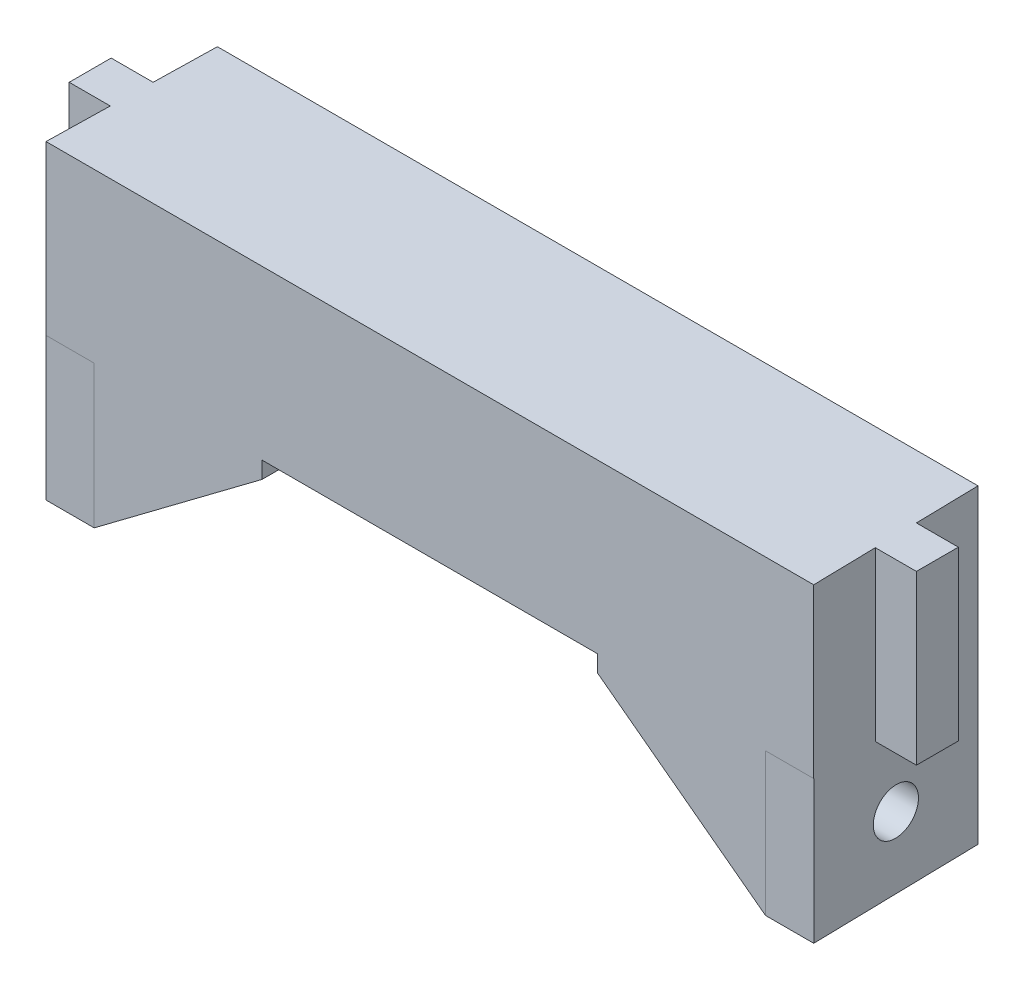
SolidWorks part; units mm, degrees
ref_plane "Front Plane" through (0, 0, 0) normal (0, 0, 1) x (1, 0, 0)
ref_plane "Top Plane" through (0, 0, 0) normal (0, 1, 0) x (1, 0, 0)
ref_plane "Right Plane" through (0, 0, 0) normal (1, 0, 0) x (0, 0, -1)
sketch "Sketch1" plane through (0, 0, 0) normal (0, 1, 0) x (1, 0, 0)
  line L0 (-45.74, 0) -> (-45.3158, 20)
  line L1 (-45.3158, 20) -> (45.3158, 20)
  line L2 (45.3158, 20) -> (45.74, 0)
  line L3 (45.74, 0) -> (-45.74, 0)
  point P4 (0, 0)
  point P7 (0, 20)
  dimension "D1" = 20
  dimension "D2" = 91.48
  dimension "D3" = 2.43
extrude "Boss-Extrude1" add sketch "Sketch1" along normal blind 20
sketch "Sketch2" plane through (0, 20, 0) normal (0, 1, 0) x (1, 0, 0)
  line L0 (45.74, 0) -> (45.3158, 20) construction
  line L1 (45.4749, 12.5) -> (50.4749, 12.5)
  line L2 (45.4749, 12.5) -> (45.4749, 7.5)
  line L3 (45.4749, 7.5) -> (50.4749, 7.5)
  line L4 (50.4749, 12.5) -> (50.4749, 7.5)
  line L5 (40.3158, 20) -> (40.3158, 0) construction
  line L6 (45.3158, 20) -> (-45.3158, 20) construction
  line L7 (-45.74, 0) -> (45.74, 0) construction
  line L8 (40.3158, 10) -> (45.5279, 10) construction
  line L9 (0, 0) -> (0, 20) construction
  line L10 (-45.4749, 7.5) -> (-50.4749, 7.5)
  line L11 (-50.4749, 12.5) -> (-50.4749, 7.5)
  line L12 (-45.4749, 12.5) -> (-50.4749, 12.5)
  line L13 (-45.4749, 12.5) -> (-45.4749, 7.5)
  point P14 (45.4749, 10)
  dimension "D1" = 5
  dimension "D2" = 5
  dimension "D3" = 5
extrude "Boss-Extrude2" add sketch "Sketch2" against normal up to surface (20 mm away) up to face at (0, 0, -10)
sketch "Sketch3" plane through (-45.7194, 0, -0.9697) normal (-0.9998, 0, -0.0212) x (-0.0212, 0, 0.9998)
  line L0 (0.9649, 0) -> (0.9649, -27.94) construction
  line L1 (-19.0346, 0) -> (0.9649, 0)
  line L2 (-19.0346, 0) -> (-19.0346, -17)
  line L3 (-19.0346, -17) -> (0.9649, -17)
  line L4 (0.9649, 0) -> (0.9649, -17)
  circle A0 centre (-9.0348, -8.5) radius 2.75 construction
  circle A1 centre (-9.0348, -8.5) radius 6.5 construction
  point P10 (-19.0346, -8.5)
  point P11 (-9.0348, 0)
  dimension "D2" = 5.5
  dimension "D3" = 13
  dimension "D1" = 17
ref_plane "Plane1" through (-40, 0, 0) normal (1, 0, 0) x (0, 0, -1)
sketch "Sketch4" plane through (-40, 0, 0) normal (1, 0, 0) x (0, 0, -1)
  line L4 (20, 0) -> (20, -17)
  line L5 (20, -17) -> (0, -17)
  line L6 (0, -17) -> (0, 0)
  line L7 (0, 0) -> (20, 0)
  line L11 (20, -17) -> (0.0049, -17) construction
  point P0 (0, 0)
loft "Loft1" add section "Sketch4" section "Sketch3" start constraint default connector at (-40, 0, -20) connector at (-45.3158, 0, -20)
ref_plane "Plane2" through (-20, 0, 0) normal (1, 0, 0) x (0, 0, -1)
sketch "Sketch5" plane through (-20, 0, 0) normal (1, 0, 0) x (0, 0, -1)
  line L1 (20, 0) -> (0, 0)
  line L2 (20, 0) -> (20, -2)
  line L3 (20, -2) -> (0, -2)
  line L4 (0, 0) -> (0, -2)
  point P5 (0, 0)
  dimension "D1" = 2
sketch "Sketch6" plane through (-40, 0, 0) normal (1, 0, 0) x (0, 0, -1)
  line L4 (20, 0) -> (0, 0)
  line L5 (0, 0) -> (0, -17)
  line L6 (0, -17) -> (20, -17)
  line L7 (20, -17) -> (20, 0)
  line L8 (20, 0) -> (0, 0)
  line L9 (0, 0) -> (0, -17)
  line L10 (0, -17) -> (20, -17)
  line L11 (20, -17) -> (20, 0)
  dimension "D1" = 0
loft "Loft3" add profiles "Sketch6", "Sketch5" connector at (-40, 0, 0) connector at (-20, 0, 0)
sketch "Sketch7" plane through (-40, 0, 0) normal (1, 0, 0) x (0, 0, -1)
  line L0 (0, 0) -> (20, 0) construction
  line L1 (20, 0) -> (20, -17) construction
  line L2 (10, 0) -> (10, -8.5) construction
  line L3 (10, -8.5) -> (20, -8.5) construction
  circle A0 centre (10, -8.5) radius 2.75
  dimension "D1" = 5.5
extrude "Cut-Extrude1" cut sketch "Sketch7" against normal through all
sketch "Sketch8" plane through (-40, 0, 0) normal (1, 0, 0) x (0, 0, -1)
  circle A0 centre (10, -8.5) radius 6.5
  circle A1 centre (10, -8.5) radius 2.75 construction
  dimension "D1" = 13
extrude "Cut-Extrude2" cut sketch "Sketch8" along normal blind 30
mirror "Mirror1" about plane through (0, 0, 0) normal (1, 0, 0) of "Cut-Extrude2", "Cut-Extrude1", "Loft3", "Loft1"
